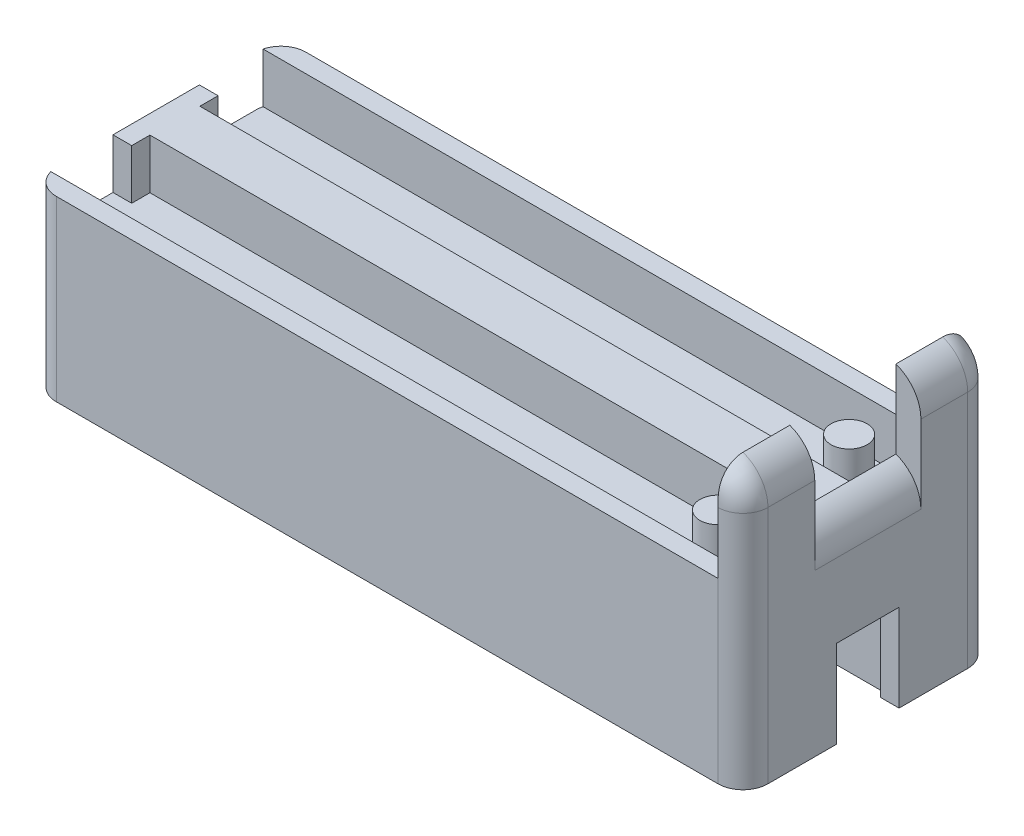
SolidWorks part; units mm, degrees
ref_plane "Front Plane" through (0, 0, 0) normal (0, 0, 1) x (1, 0, 0)
ref_plane "Top Plane" through (0, 0, 0) normal (0, 1, 0) x (1, 0, 0)
ref_plane "Right Plane" through (0, 0, 0) normal (1, 0, 0) x (0, 0, -1)
sketch "Sketch1" plane through (0, 0, 0) normal (0, 1, 0) x (1, 0, 0)
  line L1 (-69.85, -25.4) -> (69.85, -25.4)
  line L2 (-69.85, -25.4) -> (-69.85, 25.4)
  line L3 (-69.85, 25.4) -> (69.85, 25.4)
  line L4 (69.85, -25.4) -> (69.85, 25.4)
  line L5 (-69.85, -25.4) -> (69.85, 25.4) construction
  line L6 (-69.85, 25.4) -> (69.85, -25.4) construction
  point P0 (0, 0)
  dimension "D1" = 139.7
  dimension "D2" = 50.8
extrude "base" add sketch "Sketch1" along normal blind 8.255
sketch "Sketch3" plane through (0, 8.255, 0) normal (0, 1, 0) x (1, 0, 0)
  line L0 (-69.85, 25.4) -> (69.85, 25.4)
  line L1 (69.85, 25.4) -> (69.85, -25.4)
  line L2 (69.85, -25.4) -> (-69.85, -25.4)
  line L3 (-69.85, -25.4) -> (-69.85, -21.59)
  line L4 (-69.85, 25.4) -> (-69.85, -25.4) construction
  line L5 (-69.85, -21.59) -> (66.04, -21.59)
  line L6 (66.04, -21.59) -> (66.04, -5.08)
  line L8 (-69.85, -8.89) -> (-69.85, 8.89)
  line L10 (66.04, 5.08) -> (66.04, 21.59)
  line L11 (66.04, 21.59) -> (-69.85, 21.59)
  line L12 (-69.85, 21.59) -> (-69.85, 25.4)
  line L14 (-69.85, 8.89) -> (-66.04, 8.89)
  line L15 (-66.04, 8.89) -> (-66.04, 5.08)
  line L16 (-66.04, 5.08) -> (66.04, 5.08)
  line L18 (66.04, -5.08) -> (-66.04, -5.08)
  line L19 (-66.04, -5.08) -> (-66.04, -8.89)
  line L20 (-66.04, -8.89) -> (-69.85, -8.89)
  line M14 (69.85, -25.4) -> (69.85, 25.4)
  line M15 (69.85, 25.4) -> (-69.85, 25.4)
  line M16 (-69.85, 25.4) -> (-69.85, -25.4)
  line M17 (-69.85, -25.4) -> (69.85, -25.4)
  dimension "D1" = 3.81
  dimension "D2" = 12.7
  dimension "D3" = 12.7
  dimension "D4" = 3.81
extrude "mechanism walls" add sketch "Sketch3" along normal blind 10.16 contours L20 L19 L18 L6 L5 L11 L10 L16 L15 L14 M16 M17 M14 M15 region at (2.4919, 8.255, 0)
sketch "Sketch4" plane through (0, 8.255, 0) normal (0, 1, 0) x (1, 0, 0)
  line L0 (57.785, 13.335) -> (57.785, -13.335) construction
  line L1 (57.785, 13.335) -> (66.04, 13.335) construction
  line L2 (66.04, 5.08) -> (66.04, 21.59) construction
  line L3 (57.785, -13.335) -> (66.04, -13.335) construction
  line L4 (66.04, -21.59) -> (66.04, -5.08) construction
  line L5 (57.785, 13.335) -> (57.785, 21.59) construction
  line L6 (66.04, 21.59) -> (-69.85, 21.59) construction
  line L7 (57.785, -13.335) -> (57.785, -21.59) construction
  line L8 (-69.85, -21.59) -> (66.04, -21.59) construction
  circle A0 centre (57.785, 13.335) radius 3.683
  circle A1 centre (57.785, -13.335) radius 3.683
  dimension "D1" = 7.366
extrude "spring cylinders" add sketch "Sketch4" along normal up to surface (10.16 mm away) up to face at (-17.4625, 18.415, 0)
sketch "Sketch6" plane through (69.85, 0, 0) normal (1, 0, 0) x (0, 0, -1)
  line L0 (25.4, 18.415) -> (25.4, 0) construction
  line L1 (-25.4, 0) -> (25.4, 0)
  line L2 (-25.4, 0) -> (-25.4, 38.1)
  line L4 (25.4, 0) -> (25.4, 38.1)
  line L5 (-25.4, 38.1) -> (-10.795, 38.1)
  line L6 (-10.795, 38.1) -> (-10.795, 22.225)
  line L7 (-10.795, 22.225) -> (10.795, 22.225)
  line L8 (10.795, 22.225) -> (10.795, 38.1)
  line L9 (10.795, 38.1) -> (25.4, 38.1)
  line L10 (-25.4, 18.415) -> (25.4, 18.415) construction
  dimension "D1" = 3.81
  dimension "D2" = 38.1
  dimension "D3" = 21.59
extrude "wall" add sketch "Sketch6" along normal blind 5.08
sketch "Sketch7" plane through (0, 0, 0) normal (0, -1, 0) x (1, 0, 0)
  line L0 (74.93, 25.4) -> (74.93, 6.35)
  line L1 (-69.85, 25.4) -> (74.93, 25.4)
  line L2 (-69.85, 25.4) -> (-69.85, -25.4)
  line L3 (-69.85, -25.4) -> (74.93, -25.4)
  line L5 (74.93, 25.4) -> (74.93, -25.4) construction
  line L6 (74.93, 6.35) -> (71.12, 6.35)
  line L7 (71.12, 6.35) -> (71.12, 21.59)
  line L8 (71.12, 21.59) -> (-66.04, 21.59)
  line L9 (-66.04, 21.59) -> (-66.04, -21.59)
  line L10 (-66.04, -21.59) -> (71.12, -21.59)
  line L11 (71.12, -21.59) -> (71.12, -6.35)
  line L12 (71.12, -6.35) -> (74.93, -6.35)
  line L13 (74.93, -6.35) -> (74.93, -25.4)
  dimension "D1" = 3.81
  dimension "D4" = 3.81
  dimension "D2" = 3.81
  dimension "D3" = 3.81
  dimension "D5" = 12.7
  dimension "D6" = 15.24
extrude "circuit walls" add sketch "Sketch7" along normal blind 17.78
sketch "Sketch8" plane through (0, 0, 0) normal (0, -1, 0) x (1, 0, 0)
  line L0 (-52.07, 14.605) -> (-66.04, 14.605) construction
  line L1 (-66.04, 21.59) -> (-52.07, 21.59)
  line L2 (-66.04, 21.59) -> (-66.04, 7.62)
  line L3 (-66.04, 7.62) -> (-52.07, 7.62)
  line L4 (-52.07, 21.59) -> (-52.07, 7.62)
  line L5 (-59.055, 21.59) -> (-59.055, 7.62) construction
  line L6 (0, 0) -> (0, 21.59) construction
  line L7 (-66.04, 21.59) -> (71.12, 21.59) construction
  line L8 (0, 0) -> (-66.04, 0) construction
  line L9 (-66.04, -21.59) -> (-66.04, 21.59) construction
  line L10 (-66.04, -21.59) -> (-52.07, -21.59)
  line L11 (-66.04, -21.59) -> (-66.04, -7.62)
  line L12 (-52.07, -21.59) -> (-52.07, -7.62)
  line L13 (-66.04, -7.62) -> (-52.07, -7.62)
  line L14 (2.54, 21.59) -> (2.54, -21.59) construction
  line L15 (71.12, -21.59) -> (-66.04, -21.59) construction
  line L16 (64.135, 21.59) -> (64.135, 7.62) construction
  line L17 (57.15, 14.605) -> (71.12, 14.605) construction
  line L18 (71.12, -7.62) -> (57.15, -7.62)
  line L19 (57.15, -21.59) -> (57.15, -7.62)
  line L20 (71.12, -21.59) -> (71.12, -7.62)
  line L21 (71.12, -21.59) -> (57.15, -21.59)
  line L22 (57.15, 21.59) -> (57.15, 7.62)
  line L23 (71.12, 7.62) -> (57.15, 7.62)
  line L24 (71.12, 21.59) -> (71.12, 7.62)
  line L25 (71.12, 21.59) -> (57.15, 21.59)
  dimension "D2" = 13.97
  dimension "D3" = 2.54
extrude "magnet junctions" add sketch "Sketch8" along normal up to surface (17.78 mm away) up to face at (26.035, -17.78, 0)
sketch "Sketch9" plane through (0, -17.78, 0) normal (0, -1, 0) x (1, 0, 0)
  line L0 (-66.04, 7.62) -> (-66.04, 25.4) construction
  line L1 (74.93, 25.4) -> (-69.85, 25.4) construction
  line L2 (0, 0) -> (-66.04, 0) construction
  line L3 (-52.07, 14.605) -> (-66.04, 14.605) construction
  line L4 (-52.07, 7.62) -> (-52.07, 21.59) construction
  line L5 (-66.04, -7.62) -> (-66.04, 7.62) construction
  line L6 (0, 0) -> (0, 21.59) construction
  line L7 (-52.07, 21.59) -> (57.15, 21.59) construction
  line L8 (2.54, 21.59) -> (2.54, -21.59) construction
  line L9 (-52.07, 21.59) -> (57.15, 21.59) construction
  line L10 (57.15, -21.59) -> (-52.07, -21.59) construction
  line L12 (-59.055, 19.2977) -> (-63.119, 16.9514)
  line L13 (-63.119, 16.9514) -> (-63.119, 12.2586)
  line L14 (-63.119, 12.2586) -> (-59.055, 9.9123)
  line L15 (-59.055, 9.9123) -> (-54.991, 12.2586)
  line L16 (-54.991, 12.2586) -> (-54.991, 16.9514)
  line L17 (-54.991, 16.9514) -> (-59.055, 19.2977)
  line L19 (-63.119, -12.2586) -> (-59.055, -9.9123)
  line L20 (-63.119, -16.9514) -> (-63.119, -12.2586)
  line L21 (-59.055, -19.2977) -> (-63.119, -16.9514)
  line L22 (-54.991, -16.9514) -> (-59.055, -19.2977)
  line L23 (-54.991, -12.2586) -> (-54.991, -16.9514)
  line L24 (-59.055, -9.9123) -> (-54.991, -12.2586)
  line L25 (64.135, 9.9123) -> (60.071, 12.2586)
  line L26 (60.071, 12.2586) -> (60.071, 16.9514)
  line L27 (60.071, 16.9514) -> (64.135, 19.2977)
  line L28 (64.135, 19.2977) -> (68.199, 16.9514)
  line L29 (68.199, 16.9514) -> (68.199, 12.2586)
  line L30 (68.199, 12.2586) -> (64.135, 9.9123)
  line L31 (64.135, -19.2977) -> (68.199, -16.9514)
  line L32 (68.199, -16.9514) -> (68.199, -12.2586)
  line L33 (68.199, -12.2586) -> (64.135, -9.9123)
  line L34 (64.135, -9.9123) -> (60.071, -12.2586)
  line L35 (60.071, -12.2586) -> (60.071, -16.9514)
  line L36 (60.071, -16.9514) -> (64.135, -19.2977)
  circle A4 centre (-59.055, 14.605) radius 4.064 construction
  point P1 (0, 0)
  point P9 (0, 0)
  point P17 (-59.055, 14.605)
  dimension "D1" = 8.128
  dimension "D3" = 10.795
  dimension "D2" = 2.54
  dimension "D4" = 10.795
extrude "magnet holes" cut sketch "Sketch9" against normal blind 8.0772
sketch "Sketch10" plane through (0, 0, 0) normal (0, -1, 0) x (1, 0, 0)
  line L0 (-52.07, 21.59) -> (57.15, 21.59) construction
  line L1 (-52.07, -21.59) -> (-37.07, -21.59)
  line L2 (-52.07, -21.59) -> (-52.07, 21.59)
  line L3 (-52.07, 21.59) -> (-37.07, 21.59)
  line L4 (-37.07, -21.59) -> (-37.07, 21.59)
  line L5 (-52.07, -21.59) -> (-37.07, 21.59) construction
  line L6 (-52.07, 21.59) -> (-37.07, -21.59) construction
  line L8 (-52.07, 7.62) -> (-52.07, 21.59) construction
  line L9 (57.15, -21.59) -> (-52.07, -21.59) construction
  point P0 (-44.57, 0)
  dimension "D1" = 15
extrude "Boss-Extrude1" add sketch "Sketch10" along normal blind 5.334
fillet "Fillet1" radius 7.62 2 edges at (74.93, 38.1, -18.0975) (74.93, 38.1, 18.0975)
fillet "Fillet2" radius 5.08 4 edges at (74.93, 6.5679, -25.4) (74.93, 6.5679, 25.4) (73.5317, 35.3152, -25.4) (73.5317, 35.3152, 25.4)
fillet "Fillet4" radius 7.62 1 edges at (74.93, 22.225, 0)
fillet "Fillet5" radius 5.08 2 edges at (-69.85, 0.3175, -25.4) (-69.85, 0.3175, 25.4)
sketch "Sketch11" plane through (0, 0, 8.89) normal (0, 0, 1) x (1, 0, 0)
  line L1 (-69.85, 18.415) -> (-66.04, 18.415)
  line L2 (-69.85, 18.415) -> (-69.85, 8.255)
  line L3 (-69.85, 8.255) -> (-66.04, 8.255)
  line L4 (-66.04, 18.415) -> (-66.04, 8.255)
extrude "Cut-Extrude1" cut sketch "Sketch11" against normal blind 0.1016
sketch "Sketch12" plane through (0, 0, -8.89) normal (0, 0, -1) x (-1, 0, 0)
  line L1 (66.04, 18.415) -> (83.2, 18.415)
  line L2 (66.04, 18.415) -> (66.04, 8.255)
  line L3 (66.04, 8.255) -> (83.2, 8.255)
  line L4 (83.2, 18.415) -> (83.2, 8.255)
extrude "Cut-Extrude2" cut sketch "Sketch12" against normal blind 0.1016
equation "\"D3@Sketch3\"=\"D2@Sketch3\""
equation "\"D4@Sketch3\"=\"D1@Sketch3\""
equation "\"D2@Sketch7\"=\"D1@Sketch7\""
equation "\"D3@Sketch7\"=\"D1@Sketch7\""
equation "\"D4@Sketch7\"=\"D1@Sketch7\""
